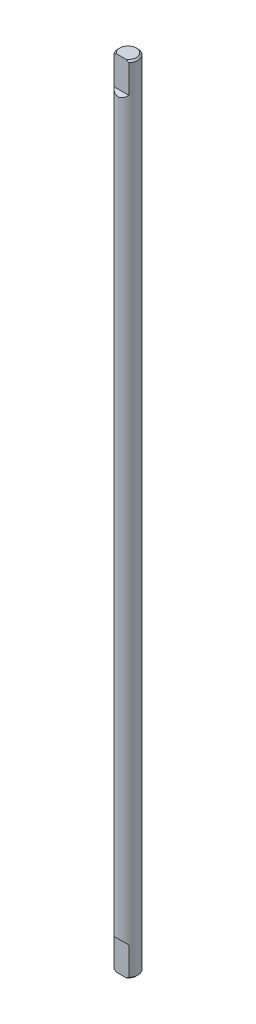
SolidWorks part; units mm, degrees
ref_plane "Ebene vorne" through (0, 0, 0) normal (0, 0, 1) x (1, 0, 0)
ref_plane "Ebene oben" through (0, 0, 0) normal (0, 1, 0) x (1, 0, 0)
ref_plane "Ebene rechts" through (0, 0, 0) normal (1, 0, 0) x (0, 0, -1)
sketch "Skizze1" plane through (0, 0, 0) normal (0, 1, 0) x (1, 0, 0)
  circle A0 centre (0, 0) radius 3
  dimension "D1" = 6
extrude "Aufsatz-Linear austragen1" add sketch "Skizze1" along normal blind 240
chamfer "Fase2" distance 0.5 angle 45 2 edges at (0, 240, 3) (0, 0, 3)
sketch "Skizze2" plane through (0, 0, 0) normal (0, 0, 1) x (1, 0, 0)
  line L0 (3, 120) -> (-3, 120) construction
  line L1 (3, 0.5) -> (3, 239.5) construction
  line L2 (-3, 239.5) -> (-3, 0.5) construction
  line L3 (3, 240) -> (3, 230)
  line L4 (-3, 0) -> (3, 0)
  line L5 (-3, 0) -> (-3, 10)
  line L6 (-3, 10) -> (3, 10)
  line L7 (3, 0) -> (3, 10)
  line L8 (-3, 230) -> (3, 230)
  line L9 (-3, 240) -> (-3, 230)
  line L10 (-3, 240) -> (3, 240)
  dimension "D1" = 10
  dimension "D2" = 0
extrude "Schnitt-Linear austragen1" cut sketch "Skizze2" along normal through all from offset 2
chamfer "Fase1" distance 1 angle 45 2 edges at (0, 230, 2) (0, 10, 2)
